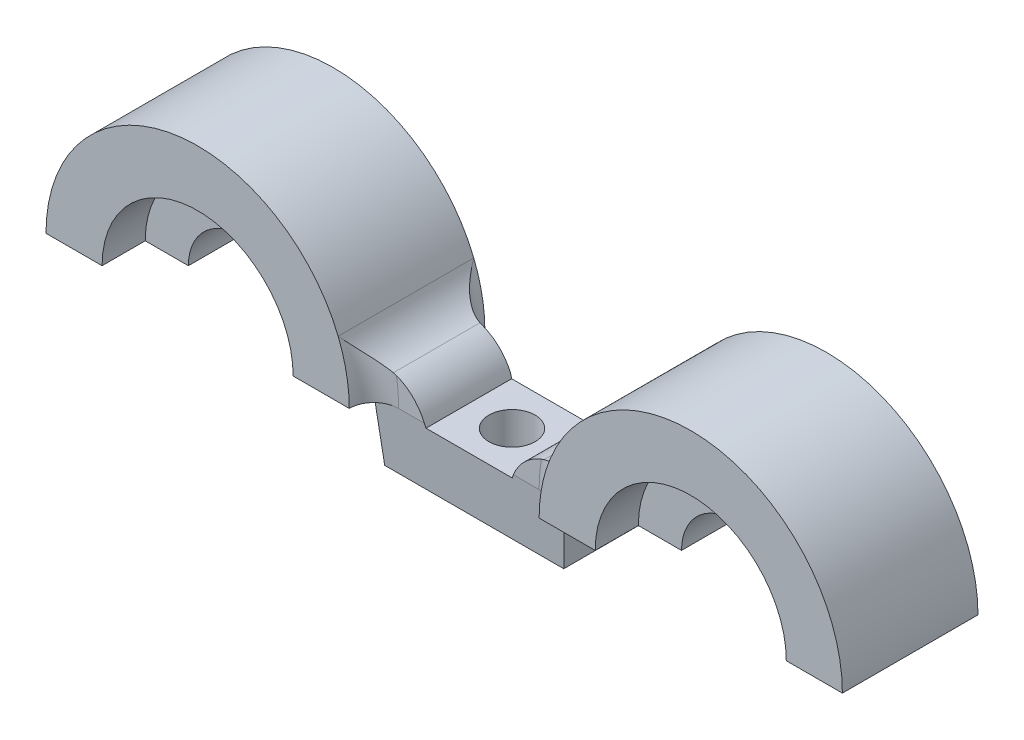
SolidWorks part; units mm, degrees
ref_plane "Alzado" through (0, 0, 0) normal (0, 0, 1) x (1, 0, 0)
ref_plane "Planta" through (0, 0, 0) normal (0, 1, 0) x (1, 0, 0)
ref_plane "Vista lateral" through (0, 0, 0) normal (1, 0, 0) x (0, 0, -1)
sketch "Croquis1" plane through (0, 0, 0) normal (0, 0, 1) x (1, 0, 0)
  line L1 (-30.32, 6) -> (30.32, 6)
  line L2 (-30.32, 6) -> (-30.32, -6)
  line L3 (-30.32, -6) -> (30.32, -6)
  line L4 (30.32, 6) -> (30.32, -6)
  line L5 (-30.32, 6) -> (30.32, -6) construction
  line L6 (-30.32, -6) -> (30.32, 6) construction
  point P0 (0, 0)
  dimension "D1" = 60.64
  dimension "D2" = 12
extrude "Saliente-Extruir1" add sketch "Croquis1" along normal mid plane 7
sketch "Croquis2" plane through (0, 0, -3.5) normal (0, 0, -1) x (-1, 0, 0)
  line L0 (30.32, -6) -> (-30.32, -6) construction
  circle A0 centre (20, -6) radius 4.25
  circle A1 centre (-20, -6) radius 4.25
  point P7 (0, -6)
  line M2 (-30.32, -6) -> (30.32, -6)
  dimension "D1" = 8.5
  dimension "D2" = 40
  dimension "D3" = 20
extrude "Cortar-Extruir1" cut sketch "Croquis2" against normal blind 10 contours A1 M2 | A1 M2 | A0 region at (20, -7.8038, -3.5) region at (20, -4.1962, -3.5)
sketch "Croquis3" plane through (0, 0, -3.5) normal (0, 0, -1) x (-1, 0, 0)
  line L0 (0, 0) -> (0, -20.6892) construction
  line L1 (0, 0) -> (-15.9907, 0) construction
  line L2 (32.3, -6) -> (7.7, -6)
  arc A0 (27.75, -6) -> (12.25, -6) centre (20, -6) ccw
  arc A1 (32.3, -6) -> (7.7, -6) centre (20, -6) ccw
  line M1 (-15.75, -6) -> (15.75, -6)
  line M4 (30.32, -6) -> (30.32, 6)
  line M5 (30.32, 6) -> (-30.32, 6)
  dimension "D1" = 15.5
  dimension "D2" = 24.6
extrude "Saliente-Extruir2" add sketch "Croquis3" along normal blind 2 and the other way blind 7 contours L2 A1 M4 | A1 A0 L2 M4 M5 M1 | A1 M5 region at (-31.1177, -3.4611, -3.5) region at (-29.035, -5.7439, -3.5) region at (-20, 6.1201, -3.5)
mirror "Simetría5" about plane through (0, 0, 0) normal (1, 0, 0) of "Saliente-Extruir2"
mirror "Simetría6" about plane through (0, 0, 0) normal (0, 0, 1) of "Simetría5", "Saliente-Extruir2"
extrude "Cortar-Extruir2" cut sketch "Croquis3<3>" against normal through all both and the other way through all contours A1 M4 M5 region at (-28.1942, 4.4591, -3.5)
sketch "Croquis3<3>" plane through (0, 0, -3.5) normal (0, 0, -1) x (-1, 0, 0) same geometry as "Croquis3"
mirror "Simetría7" about plane through (0, 0, 0) normal (1, 0, 0) of "Cortar-Extruir2"
sketch "Croquis6" plane through (0, 0, 0) normal (0, 0, 1) x (1, 0, 0)
  line L0 (-7.9567, -3.5) -> (7.9567, -3.5)
  line L2 (17.3, 6) -> (-17.3, 6)
  line L3 (-7.7, -6) -> (7.7, -6)
  line L4 (17.3, 6) -> (-17.3, 6)
  line L5 (-7.7, -6) -> (7.7, -6)
  arc A2 (17.3, 6) -> (7.7, -6) centre (20, -6) ccw
  arc A3 (-7.7, -6) -> (-17.3, 6) centre (-20, -6) ccw
  arc A4 (17.3, 6) -> (7.7, -6) centre (20, -6) ccw
  arc A5 (-7.7, -6) -> (-17.3, 6) centre (-20, -6) ccw
  dimension "D2" = 2.5
  dimension "D1" = 0
extrude "Cortar-Extruir5" cut sketch "Croquis6" against normal through all both and the other way through all contours A5 L0 A4 L4 region at (0, 1.8412, 0)
sketch "Croquis4" plane through (0, -3.5, 0) normal (0, 1, 0) x (1, 0, 0)
  line L1 (-3.5, -3.5) -> (3.5, -3.5)
  line L2 (3.5, -3.5) -> (3.5, 3.5)
  line L3 (-7.9567, -3.5) -> (7.9567, -3.5) construction
  line L4 (-7.9567, 3.5) -> (7.9567, 3.5) construction
  line L5 (-3.5, -3.5) -> (-3.5, 3.5)
  line L6 (3.5, 3.5) -> (-3.5, 3.5)
  circle A1 centre (0, 0) radius 1.875
  point P4 (0, 0)
  line M22 (-7.9567, -3.5) -> (7.9567, -3.5)
  line M24 (7.9567, 3.5) -> (-7.9567, 3.5)
  dimension "D2" = 7
  dimension "D1" = 3.75
  dimension "D3" = 3.5
sketch "Croquis7" plane through (0, -6, 0) normal (0, -1, 0) x (1, 0, 0)
  line L1 (7.7, -3.5) -> (-7.7, -3.5)
  line L2 (7.7, -3.5) -> (7.7, 3.5)
  line L3 (7.7, 3.5) -> (-7.7, 3.5)
  line L4 (-7.7, -3.5) -> (-7.7, 3.5)
  line L5 (7.7, -3.5) -> (-7.7, 3.5) construction
  line L6 (7.7, 3.5) -> (-7.7, -3.5) construction
  point P0 (0, 0)
extrude "Saliente-Extruir3" add sketch "Croquis7" along normal blind 5 draft 5
extrude "Cortar-Extruir13" cut sketch "Croquis4" against normal blind 2.8 contours L5 L2 A1 M22 M24 | A1
extrude "Cortar-Extruir14" cut sketch "Croquis4<6>" against normal through all both and the other way through all contours A1 region at (0, -3.5, 0)
sketch "Croquis4<6>" plane through (0, -3.5, 0) normal (0, 1, 0) x (1, 0, 0) same geometry as "Croquis4"
fillet "Redondeo1" radius 4 2 edges at (-3.5, -3.5, 0) (3.5, -3.5, 0)
fillet "Redondeo2" radius 4 2 edges at (7.9567, -3.5, 0) (-7.9567, -3.5, 0)
fillet "Redondeo6" radius 2 4 edges at (-7.9274, -3.6456, -3.5) (7.9274, -3.6456, -3.5) (7.9274, -3.6456, 3.5) (-7.9274, -3.6456, 3.5)
sketch "Croquis8" plane through (0, 0, 3.5) normal (0, 0, 1) x (1, 0, 0)
  line L0 (-27.75, -6) -> (-24.25, -6) construction
  line L1 (-15.75, -6) -> (-12.25, -6) construction
  line L2 (24.25, -6) -> (27.75, -6) construction
  line L3 (12.25, -6) -> (15.75, -6) construction
  line L4 (-27.75, -6) -> (-24.25, -6)
  line L5 (-15.75, -6) -> (-12.25, -6)
  line L6 (24.25, -6) -> (27.75, -6)
  line L7 (12.25, -6) -> (15.75, -6)
  arc A0 (-12.25, -6) -> (-27.75, -6) centre (-20, -6) ccw construction
  arc A1 (-15.75, -6) -> (-24.25, -6) centre (-20, -6) ccw construction
  arc A2 (27.75, -6) -> (12.25, -6) centre (20, -6) ccw construction
  arc A3 (24.25, -6) -> (15.75, -6) centre (20, -6) ccw construction
  arc A4 (-12.25, -6) -> (-27.75, -6) centre (-20, -6) ccw
  arc A5 (-15.75, -6) -> (-24.25, -6) centre (-20, -6) ccw
  arc A6 (27.75, -6) -> (12.25, -6) centre (20, -6) ccw
  arc A7 (24.25, -6) -> (15.75, -6) centre (20, -6) ccw
extrude "Cortar-Extruir15" cut sketch "Croquis8" against normal blind 1.5
mirror "Simetría8" about plane through (0, 0, 0) normal (0, 0, 1) of "Cortar-Extruir15"
